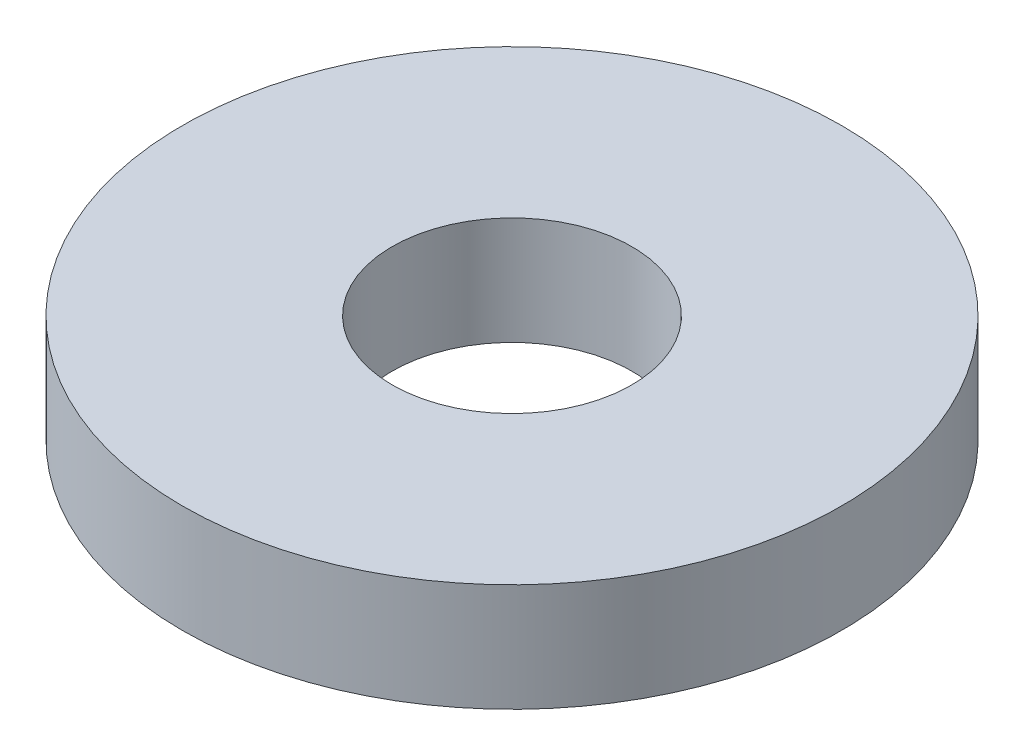
SolidWorks part; units mm, degrees
ref_plane "Front Plane" through (0, 0, 0) normal (0, 0, 1) x (1, 0, 0)
ref_plane "Top Plane" through (0, 0, 0) normal (0, 1, 0) x (1, 0, 0)
ref_plane "Right Plane" through (0, 0, 0) normal (1, 0, 0) x (0, 0, -1)
sketch "Sketch1" plane through (0, 0, 0) normal (0, 1, 0) x (1, 0, 0)
  circle A0 centre (0, 0) radius 27.5
  dimension "FLANGE_OD" = 55
extrude "Boss-Extrude1" add sketch "Sketch1" along normal blind 9
sketch "Sketch2" plane through (0, 0, 0) normal (0, 1, 0) x (1, 0, 0)
  circle A0 centre (0, 0) radius 10
  dimension "BORE_D" = 20
extrude "Cut-Extrude1" cut sketch "Sketch2" along normal through all
sketch "Sketch3" plane through (0, 9, 0) normal (0, 1, 0) x (1, 0, 0)
  circle A0 centre (0, 0) radius 7.2684 construction
  circle A1 centre (-7.2684, 0) radius 2.6514
  dimension "BOLT_D" = 5.3028
  dimension "BOLT_PCD" = 14.5369
extrude "Cut-Extrude2" cut sketch "Sketch3" against normal blind 6.7791 rebuild error yes
pattern_circular "CirPattern1" count 3 over 360 rebuild error yes
